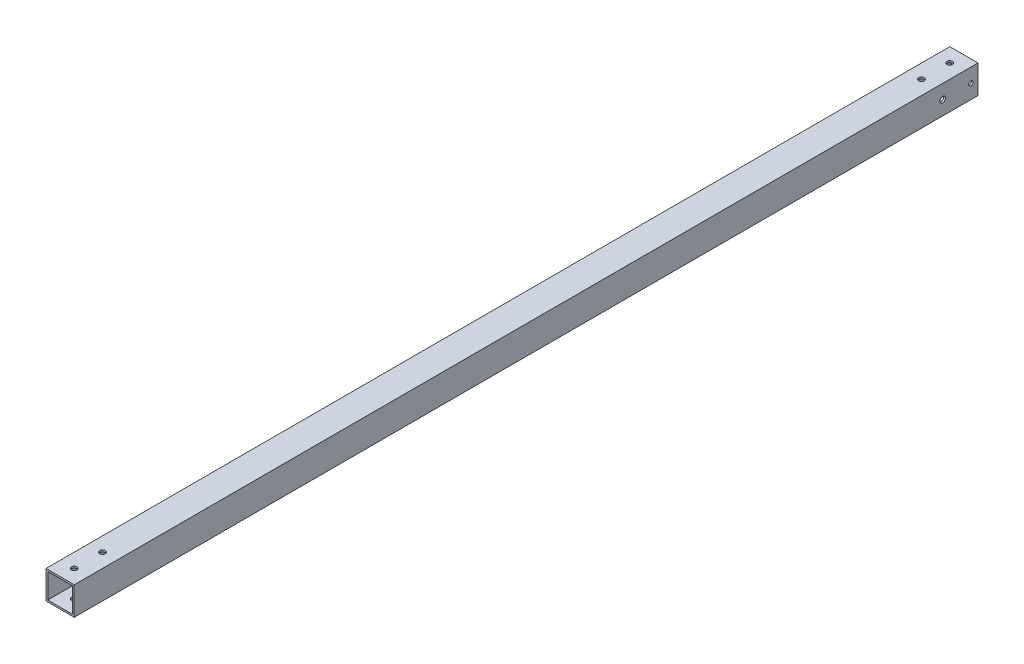
SolidWorks part; units mm, degrees
ref_plane "Front Plane" through (0, 0, 0) normal (0, 0, 1) x (1, 0, 0)
ref_plane "Top Plane" through (0, 0, 0) normal (0, 1, 0) x (1, 0, 0)
ref_plane "Right Plane" through (0, 0, 0) normal (1, 0, 0) x (0, 0, -1)
sketch "Sketch1" plane through (0, 0, 0) normal (0, 0, 1) x (1, 0, 0)
  line L1 (0, 0) -> (25.4, 0)
  line L2 (0, 0) -> (0, 25.4)
  line L3 (0, 25.4) -> (25.4, 25.4)
  line L4 (25.4, 0) -> (25.4, 25.4)
  line L5 (1.5875, 1.5875) -> (23.8125, 1.5875)
  line L6 (1.5875, 1.5875) -> (1.5875, 23.8125)
  line L7 (1.5875, 23.8125) -> (23.8125, 23.8125)
  line L8 (23.8125, 1.5875) -> (23.8125, 23.8125)
  dimension "D1" = 25.4
  dimension "D2" = 1.5875
  dimension "D3" = 1.5875
  dimension "D4" = 1.5875
  dimension "D5" = 1.5875
extrude "Boss-Extrude1" add sketch "Sketch1" along normal blind 812.8
sketch "Sketch3" plane through (0, 25.4, 0) normal (0, 1, 0) x (1, 0, 0)
  line L0 (0, -406.4) -> (25.4, -406.4) construction
  line L1 (25.4, -812.8) -> (25.4, 0) construction
  line L2 (25.4, 0) -> (0, 0) construction
  line L4 (0, -812.8) -> (0, 0) construction
  circle A1 centre (12.7, -12.7) radius 2.54
  circle A5 centre (12.7, -38.1) radius 2.54
  circle A12 centre (12.7, -774.7) radius 2.54
  circle A13 centre (12.7, -800.1) radius 2.54
  dimension "D1" = 5.08
  dimension "D4" = 12.7
  dimension "D7" = 25.4
extrude "Cut-Extrude2" cut sketch "Sketch3" against normal through all
sketch "Sketch4" plane through (25.4, 0, 0) normal (1, 0, 0) x (0, 0, -1)
  line L2 (0, 0) -> (0, 25.4) construction
  line L3 (-812.8, 25.4) -> (0, 25.4) construction
  circle A1 centre (-6.35, 12.7) radius 2.0034
  circle A2 centre (-31.75, 12.7) radius 2.54
  point P8 (0, 0)
  point P9 (0, 0)
  point P12 (0, 0)
  dimension "D3" = 6.35
  dimension "D1" = 5.08
  dimension "D2" = 25.4
  dimension "D4" = 12.7
extrude "Cut-Extrude3" cut sketch "Sketch4" against normal up to next
sketch "Sketch5" plane through (0, 0, 0) normal (-1, 0, 0) x (0, 0, 1)
  line L0 (0, 12.7) -> (812.8, 12.7) construction
  line L1 (0, 25.4) -> (0, 0) construction
  line L2 (812.8, 25.4) -> (812.8, 0) construction
  circle A0 centre (39.6875, 12.7) radius 2.54
  circle A1 centre (730.25, 12.7) radius 2.54
  circle A2 centre (755.65, 12.7) radius 2.54
  dimension "D1" = 5.08
  dimension "D2" = 39.6875
  dimension "D3" = 25.4
  dimension "D4" = 57.15
extrude "Cut-Extrude4" cut sketch "Sketch5" against normal up to next
